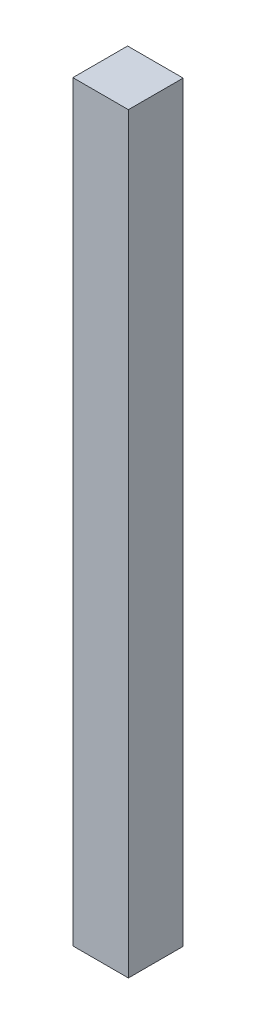
SolidWorks part; units mm, degrees
ref_plane "Front Plane" through (0, 0, 0) normal (0, 0, 1) x (1, 0, 0)
ref_plane "Top Plane" through (0, 0, 0) normal (0, 1, 0) x (1, 0, 0)
ref_plane "Right Plane" through (0, 0, 0) normal (1, 0, 0) x (0, 0, -1)
sketch "Sketch1" plane through (0, 0, 0) normal (0, 1, 0) x (1, 0, 0)
  line L1 (-22.51, -22.1884) -> (22.51, -22.1884)
  line L2 (-22.51, -22.1884) -> (-22.51, 22.1884)
  line L3 (-22.51, 22.1884) -> (22.51, 22.1884)
  line L4 (22.51, -22.1884) -> (22.51, 22.1884)
  line L5 (-22.51, -22.1884) -> (22.51, 22.1884) construction
  line L6 (-22.51, 22.1884) -> (22.51, -22.1884) construction
  point P0 (0, 0)
  dimension "D1" = 45.02
extrude "Boss-Extrude1" add sketch "Sketch1" along normal blind 609.6
